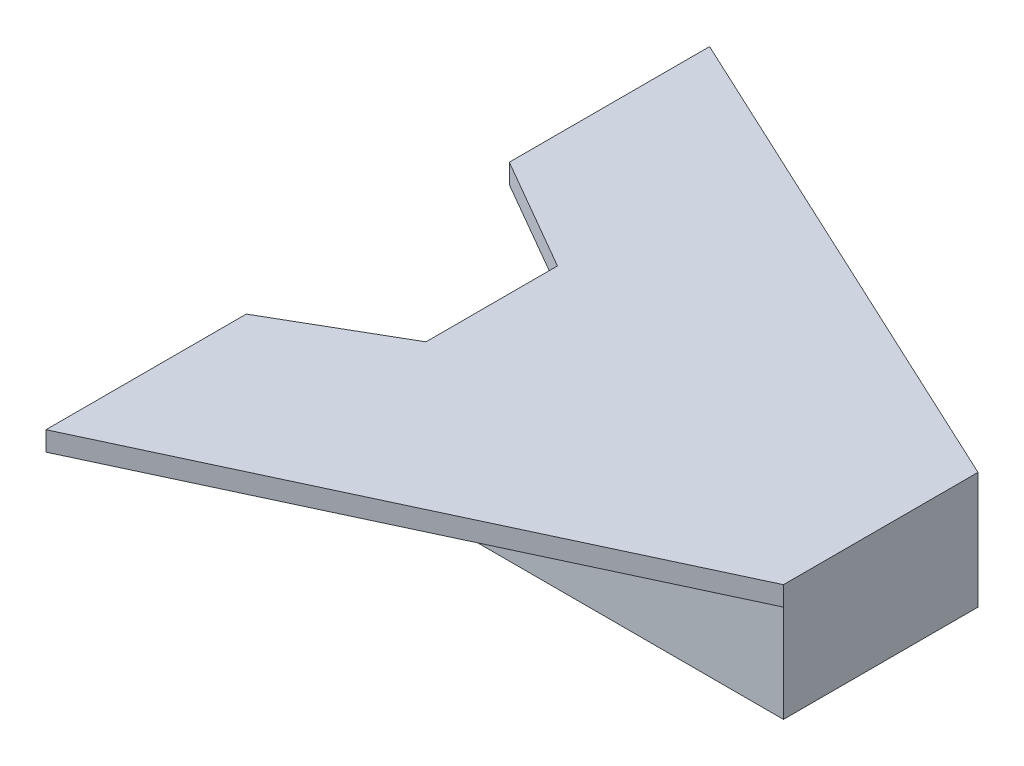
SolidWorks part; units mm, degrees
ref_plane "Front Plane" through (0, 0, 0) normal (0, 0, 1) x (1, 0, 0)
ref_plane "Top Plane" through (0, 0, 0) normal (0, 1, 0) x (1, 0, 0)
ref_plane "Right Plane" through (0, 0, 0) normal (1, 0, 0) x (0, 0, -1)
sketch "Sketch1" plane through (0, 0, 0) normal (0, 1, 0) x (1, 0, 0)
  line L0 (0, 500) -> (-1292.7596, 1102.8237)
  line L1 (0, 0) -> (-1000, 0)
  line L2 (0, 0) -> (0, 500)
  line L3 (0, 500) -> (-1000, 500)
  line L4 (-1000, 0) -> (-1000, 500)
  line L5 (-1292.7596, 1102.8237) -> (-1292.7596, 588.0497)
  line L6 (0, 250) -> (-1000, 250) construction
  line L7 (0, 0) -> (-1000, 0)
  line L11 (-1292.7596, -88.0497) -> (-1000, 80.9752)
  line L12 (-1000, 80.9752) -> (-1000, 419.0248)
  line L13 (-1000, 419.0248) -> (-1292.7596, 588.0497)
  line L14 (0, 0) -> (-1292.7596, -602.8237)
  line L15 (-1292.7596, -88.0497) -> (-1292.7596, -602.8237)
  line L16 (-1585.5192, 250) -> (-1585.5192, 80.9752) [skipped]
  line L17 (-1439.1394, -3.5373) -> (-1292.7596, -88.0497) [skipped]
  line L18 (-1292.7596, 588.0497) -> (-1439.1394, 503.5373) [skipped]
  dimension "D1" = 500
  dimension "D2" = 25
  dimension "D3" = 1000
  dimension "D4" = 0
extrude "Boss-Extrude1" add sketch "Sketch1" along normal blind 50 contours L13 L4 L3 L0 L5 | L6 L2 L3 L4 L12 | L2 L6 L4 L1 | L11 L15 L14 L1 L4 region at (-857.975, 0, -700.5752) region at (-500, 0, -375) region at (-500, 0, -125) region at (-857.975, 0, 200.5752)
sketch "Sketch2" plane through (0, 0, 0) normal (0, -1, 0) x (1, 0, 0)
  line L0 (-1000, -80.9752) -> (-1000, -419.0248) construction
  line L1 (0, 0) -> (-950, 0)
  line L2 (0, 0) -> (0, -500)
  line L3 (0, -500) -> (-950, -500)
  line L4 (-950, 0) -> (-950, -500)
  dimension "D1" = 50
extrude "Boss-Extrude2" add sketch "Sketch2" along normal blind 250
sketch "Sketch3" plane through (0, 0, 0) normal (0, 0, 1) x (1, 0, 0)
  line L0 (-950, -250) -> (-950, 0) construction
  line L1 (0, -250) -> (-950, -250) construction
  circle A0 centre (-700, -170) radius 5
  dimension "D1" = 10
  dimension "D2" = 250
  dimension "D3" = 80
extrude "Cut-Extrude1" cut sketch "Sketch3" against normal up to surface (500 mm away) up to face at (-475, -125, -500)
